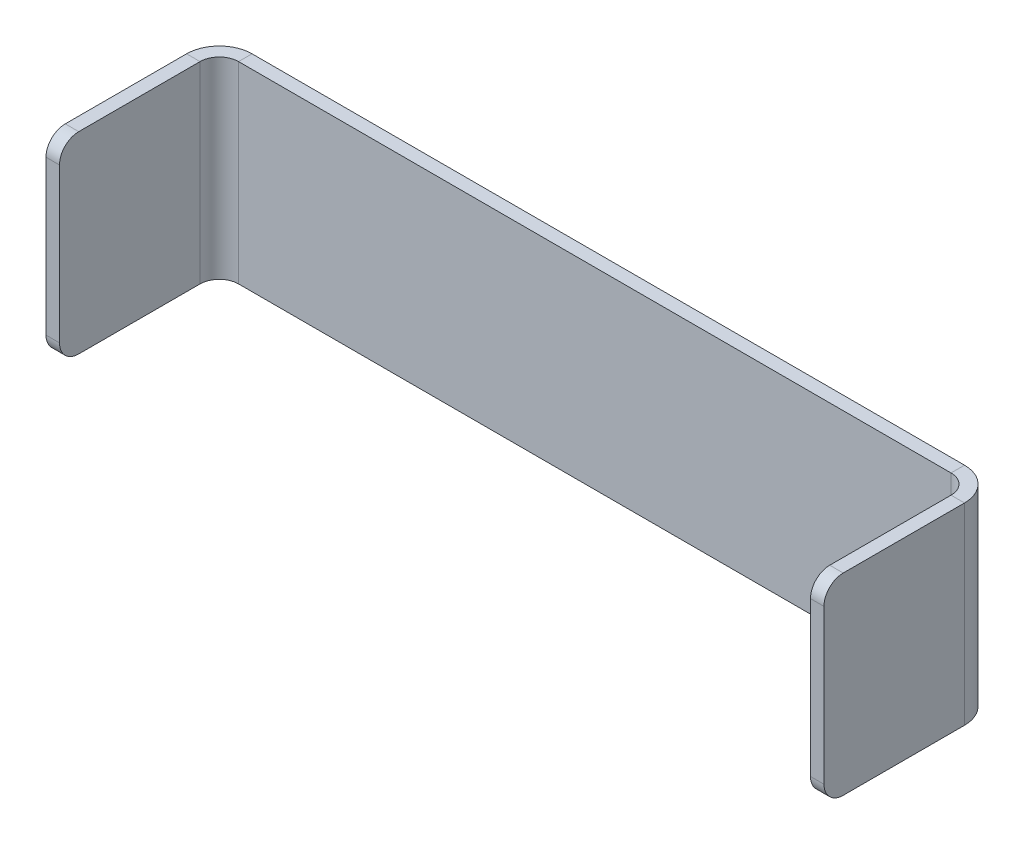
SolidWorks part; units mm, degrees
note: The reader was unsure of these and kept them because the rebuilt part matched: flange length of "Edge-Flange1", "Edge-Flange2".
material "1060 Alloy"
ref_plane "Front Plane" through (0, 0, 0) normal (0, 0, 1) x (1, 0, 0)
ref_plane "Top Plane" through (0, 0, 0) normal (0, 1, 0) x (1, 0, 0)
ref_plane "Right Plane" through (0, 0, 0) normal (1, 0, 0) x (0, 0, -1)
sketch "Sketch2" plane through (0, 0, 0) normal (0, 0, 1) x (1, 0, 0)
  line L1 (-19.5, 5) -> (19.5, 5)
  line L2 (-19.5, 5) -> (-19.5, -5)
  line L3 (-19.5, -5) -> (19.5, -5)
  line L4 (19.5, 5) -> (19.5, -5)
  line L5 (-19.5, 5) -> (19.5, -5) construction
  line L6 (-19.5, -5) -> (19.5, 5) construction
  point P0 (0, 0)
  dimension "D1" = 39
  dimension "D2" = 10
base flange "Base-Flange1" sketch "Sketch2" thickness 0.7 reverse thickness direction no parameters "D1"=1
edge flange "Edge-Flange1" sketch "Sketch9" flange angle 90 flange length 9 flange position material outside bend radius 1 thickness 0.7 relief rectangular parameters "D6"=10
sketch "Sketch9" plane through (-19.5, 0, 0) normal (-1, 0, 0) x (0, -1, 0)
  line L0 (-5, 0) -> (5, 0) construction
  line L1 (-5, 0) -> (5, 0)
  line L2 (-5, 0) -> (-5, 8.3)
  line L3 (-5, 8.3) -> (5, 8.3)
  line L4 (5, 8.3) -> (5, 0)
bend "EdgeBend1" bend radius 1 bend angle 90 parameters "D5"=1
edge flange "Edge-Flange2" sketch "Sketch12" flange angle 90 flange length 9 flange position material outside bend radius 1 thickness 0.7 relief rectangular parameters "D6"=10
sketch "Sketch12" plane through (19.5, 0, 0) normal (1, 0, 0) x (0, 1, 0)
  line L0 (-5, 0) -> (5, 0) construction
  line L1 (-5, 0) -> (5, 0)
  line L2 (-5, 0) -> (-5, 8.3)
  line L3 (-5, 8.3) -> (5, 8.3)
  line L4 (5, 8.3) -> (5, 0)
bend "EdgeBend2" bend radius 1 bend angle 90 parameters "D5"=2
fillet "Fillet1" radius 1 4 edges at (-19.85, -5, 8.3) (-19.85, 5, 8.3) (19.85, -5, 8.3) (19.85, 5, 8.3)
sketch "Bend-Lines1" [suppressed] plane through (0, 0, 0) normal (0, 1, 0) x (1, 0, 0)
sketch "Bounding-Box1" [suppressed] plane through (0, 0, 0) normal (0, 1, 0) x (1, 0, 0)
sheet metal parameters "Sheet-Metal1" thickness 0.7 parameters "D1"=1
flat pattern "Flat-Pattern1" [suppressed]
sketch "Bend-Lines2" plane through (0, 0, 0) normal (0, 1, 0) x (1, 0, 0)
sketch3d "Bounding-Box2" [suppressed]
  line L0 (19.5, -5, 0) -> (-19.5, -5, 0) construction
  line L1 (19.5, 5, 0) -> (-19.5, 5, 0) construction
  line L2 (19.5, -5, 0) -> (19.5, 5, 0) construction
  line L3 (-19.5, -5, 0) -> (-19.5, 5, 0) construction
sheet metal parameters "Sheet-Metal2" thickness 0.7 parameters "D1"=1
flat pattern "Flat-Pattern1"
sketch "Bend-Lines2" plane through (0, 0, 0) normal (0, 0, 1) x (1, 0, 0)
  line L0 (-19.5603, 5) -> (-19.5603, -5) construction
  line L1 (-19.5603, 5) -> (-19.5603, -5) construction
sketch3d "Bounding-Box2" [suppressed]
  line L0 (-25.9206, -5, 0) -> (19.5, -5, 0) construction
  line L1 (-25.9206, 5, 0) -> (19.5, 5, 0) construction
  line L2 (-25.9206, -5, 0) -> (-25.9206, 5, 0) construction
  line L3 (19.5, -5, 0) -> (19.5, 5, 0) construction
bend of the flat pattern "Flatten-<EdgeBend1>1"
sheet metal parameters "Sheet-Metal3" thickness 0.7 parameters "D1"=1
flat pattern "Flat-Pattern1"
sketch "Bend-Lines2" plane through (0, 0, 0) normal (0, 0, 1) x (1, 0, 0)
  line L0 (-19.5603, 5) -> (-19.5603, -5) construction
  line L1 (-19.5603, 5) -> (-19.5603, -5) construction
  line L2 (19.5603, -5) -> (19.5603, 5) construction
  line L3 (19.5603, -5) -> (19.5603, 5) construction
sketch3d "Bounding-Box2" [suppressed]
  line L0 (-27.9206, -5, 0) -> (27.9206, -5, 0) construction
  line L1 (-27.9206, 5, 0) -> (27.9206, 5, 0) construction
  line L2 (-27.9206, -5, 0) -> (-27.9206, 5, 0) construction
  line L3 (27.9206, -5, 0) -> (27.9206, 5, 0) construction
bend of the flat pattern "Flatten-<EdgeBend1>1"
bend of the flat pattern "Flatten-<EdgeBend2>1"
